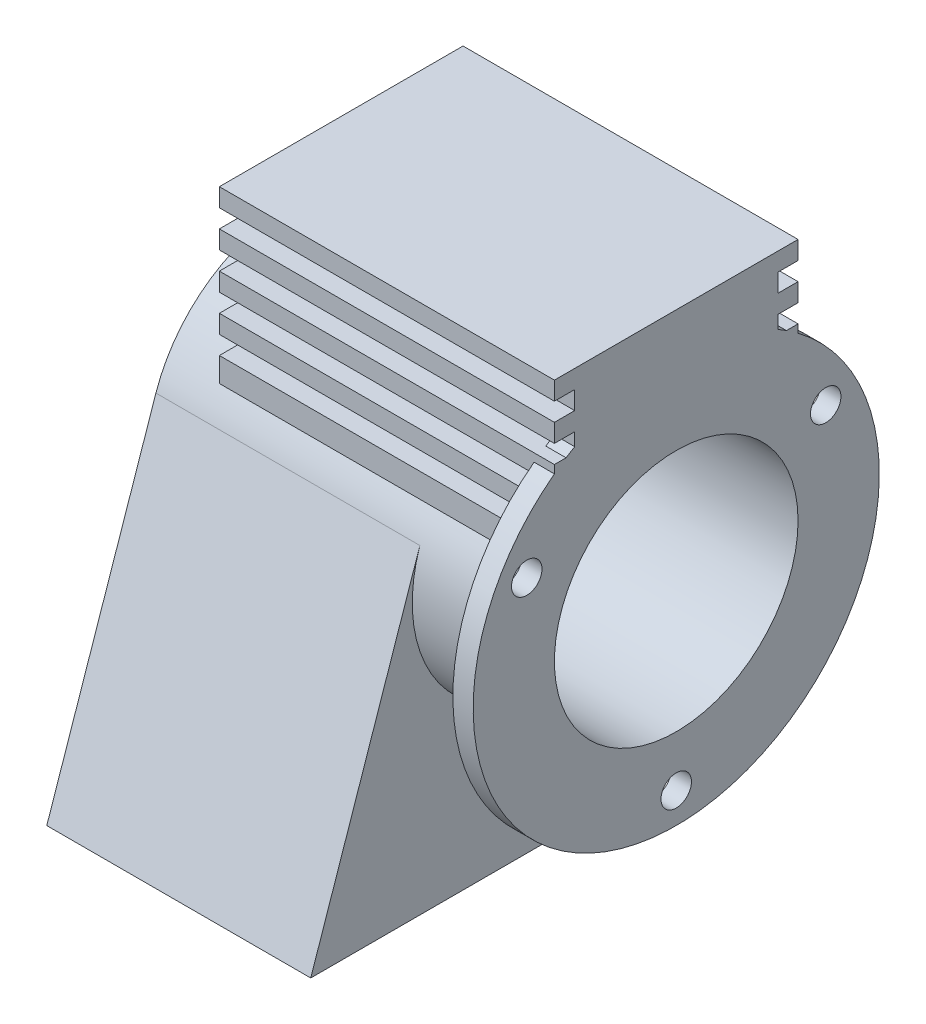
SolidWorks part; units mm, degrees
ref_plane "Front Plane" through (0, 0, 0) normal (0, 0, 1) x (1, 0, 0)
ref_plane "Top Plane" through (0, 0, 0) normal (0, 1, 0) x (1, 0, 0)
ref_plane "Right Plane" through (0, 0, 0) normal (1, 0, 0) x (0, 0, -1)
sketch "Sketch1" plane through (0, 0, 0) normal (1, 0, 0) x (0, 0, -1)
  line L0 (0, 0) -> (0, 132971.1347) construction
  line L1 (0, 0) -> (132971.1347, 0) construction
  line L2 (-152.4, 0) -> (152.4, 0)
  line L3 (-152.4, 0) -> (-84.1413, 200.1459)
  line L4 (152.4, 0) -> (84.1413, 200.1459)
  circle A0 centre (0, 171.45) radius 88.9
  point P8 (0, 0)
  point P12 (0, 0)
  dimension "D2" = 177.8
  dimension "D3" = 171.45
  dimension "D1" = 304.8
extrude "Boss-Extrude1" add sketch "Sketch1" along normal blind 165.1 contours A0 L3 L2 L4 region at (0, 56.537, 0)
extrude "Boss-Extrude2" add sketch "Sketch1<3>" along normal blind 228.6 contours A0 region at (0, 171.45, 0)
sketch "Sketch1<3>" plane through (0, 0, 0) normal (1, 0, 0) x (0, 0, -1) same geometry as "Sketch1"
sketch "Sketch2" plane through (228.6, 0, 0) normal (1, 0, 0) x (0, 0, -1)
  circle A0 centre (0, 171.45) radius 127
  dimension "D1" = 254
extrude "Boss-Extrude3" add sketch "Sketch2" along normal blind 12.7
sketch "Sketch3" plane through (241.3, 0, 0) normal (1, 0, 0) x (0, 0, -1)
  line L0 (0, 0) -> (0, 50000) construction
  line L1 (-76.2, 217.2405) -> (-76.2, 232.41)
  line L2 (-76.2, 232.41) -> (-64.7077, 232.41)
  line L3 (-63.5, 233.667) -> (-63.5, 243.84)
  line L4 (-63.5, 243.84) -> (-76.2, 243.84)
  line L5 (-76.2, 243.84) -> (-76.2, 255.27)
  line L6 (-76.2, 255.27) -> (-63.5, 255.27)
  line L7 (-63.5, 255.27) -> (-63.5, 266.7)
  line L8 (-63.5, 266.7) -> (-76.2, 266.7)
  line L9 (-76.2, 266.7) -> (-76.2, 278.13)
  line L10 (-76.2, 278.13) -> (-63.5, 278.13)
  line L11 (-63.5, 278.13) -> (-63.5, 289.56)
  line L12 (-63.5, 289.56) -> (-76.2, 289.56)
  line L13 (-76.2, 289.56) -> (-76.2, 300.99)
  line L14 (-76.2, 300.99) -> (-63.5, 300.99)
  line L15 (-63.5, 300.99) -> (-63.5, 312.42)
  line L16 (-63.5, 312.42) -> (-76.2, 312.42)
  line L17 (-76.2, 312.42) -> (-76.2, 323.85)
  line L18 (-76.2, 323.85) -> (76.2, 323.85)
  line L19 (76.2, 217.2405) -> (76.2, 232.41)
  line L20 (76.2, 232.41) -> (64.7077, 232.41)
  line L21 (63.5, 233.667) -> (63.5, 243.84)
  line L22 (63.5, 243.84) -> (76.2, 243.84)
  line L23 (76.2, 243.84) -> (76.2, 255.27)
  line L24 (76.2, 255.27) -> (63.5, 255.27)
  line L25 (63.5, 255.27) -> (63.5, 266.7)
  line L26 (63.5, 266.7) -> (76.2, 266.7)
  line L27 (76.2, 266.7) -> (76.2, 278.13)
  line L28 (76.2, 278.13) -> (63.5, 278.13)
  line L29 (63.5, 278.13) -> (63.5, 289.56)
  line L30 (63.5, 289.56) -> (76.2, 289.56)
  line L31 (76.2, 289.56) -> (76.2, 300.99)
  line L32 (76.2, 300.99) -> (63.5, 300.99)
  line L33 (63.5, 300.99) -> (63.5, 312.42)
  line L34 (63.5, 312.42) -> (76.2, 312.42)
  line L35 (76.2, 312.42) -> (76.2, 323.85)
  circle A0 centre (0, 171.45) radius 127 construction
  circle A1 centre (0, 171.45) radius 88.9 construction
  arc A2 (76.2, 217.2405) -> (64.7077, 232.41) centre (0, 171.45) ccw
  arc A3 (-64.7077, 232.41) -> (-76.2, 217.2405) centre (0, 171.45) ccw
  arc A4 (63.5, 233.667) -> (-63.5, 233.667) centre (0, 171.45) ccw
  point P17 (53.8982, 334.0778)
  point P25 (-76.2, 213.734)
  point P26 (0, 0)
  dimension "D1" = 12.7
  dimension "D2" = 11.43
  dimension "D3" = 152.4
  dimension "D4" = 152.4
  dimension "D5" = 11.43
  dimension "D6" = 12.7
  dimension "D7" = 11.43
extrude "Boss-Extrude4" add sketch "Sketch3" against normal blind 209.55
hole_wizard "CBORE for #00 Binding Head Machine Screw1" positions "Sketch4" profile "Sketch5" counterbore size "#00" standard "ANSI Inch" end condition through all
sketch "Sketch4" plane through (241.3, 0, 0) normal (1, 0, 0) x (0, 0, -1)
  point P0 (0, 171.45)
sketch "Sketch5" plane through (241.3, 171.45, 0) normal (0, 1, 0) x (0, 0, -1)
  line L0 (0, 0) -> (0, 241.3)
  line L1 (0, 241.3) -> (19.05, 241.3)
  line L3 (19.05, 241.3) -> (19.05, 228.6)
  line L4 (19.05, 228.6) -> (76.2, 228.6)
  line L5 (76.2, 228.6) -> (76.2, 0)
  line L7 (76.2, 0) -> (0, 0)
  line L11 (0, -6.35) -> (0, 107.95) construction
  dimension "Thru Hole Dia." = 38.1
  dimension "Thru Hole Depth" = 241.3
  dimension "C'Bore Dia." = 152.4
  dimension "C'Bore Depth" = 228.6
hole_wizard "#97 (0.75) Diameter Hole1" positions "Sketch7" profile "Sketch8" hole size "#97" standard "ANSI Inch" end condition up to next
sketch "Sketch7" plane through (241.3, 0, 0) normal (1, 0, 0) x (0, 0, -1)
  circle A0 centre (0, 171.45) radius 107.95 construction
  point P0 (0, 63.5)
  dimension "D1" = 215.9
sketch "Sketch8" plane through (241.3, 63.5, 0) normal (0, 1, 0) x (0, 0, -1)
  line L0 (0, 0) -> (0, 12.7)
  line L1 (0, 12.7) -> (9.525, 12.7)
  line L2 (9.525, 12.7) -> (9.525, 0)
  line L5 (9.525, 0) -> (0, 0)
  line L11 (0, -6.35) -> (0, 107.95) construction
  dimension "Thru Hole Dia." = 19.05
  dimension "Thru Hole Depth" = 12.7
pattern_circular "CirPattern1" count 3 over 360 about axis through (241.3, 171.45, 0) along (1, 0, 0) of "#97 (0.75) Diameter Hole1" reverse direction yes
